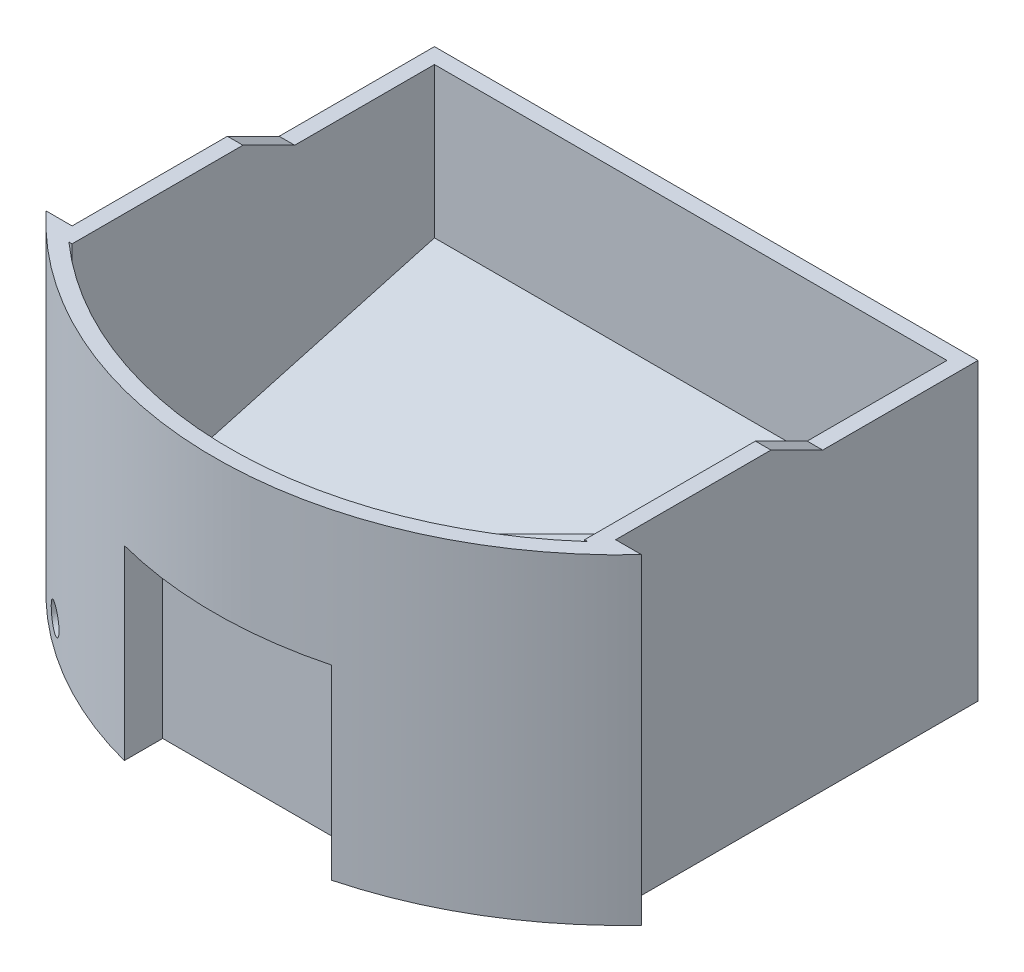
SolidWorks part; units mm, degrees
ref_plane "Front Plane" through (0, 0, 0) normal (0, 0, 1) x (1, 0, 0)
ref_plane "Top Plane" through (0, 0, 0) normal (0, 1, 0) x (1, 0, 0)
ref_plane "Right Plane" through (0, 0, 0) normal (1, 0, 0) x (0, 0, -1)
sketch "Sketch4" plane through (0, 0, 0) normal (0, 1, 0) x (1, 0, 0)
  line L0 (-6.35, 0) -> (139.7, 0)
  line L1 (0, 0) -> (133.35, 0)
  line L2 (0, 0) -> (0, 88.9)
  line L3 (0, 88.9) -> (133.35, 88.9)
  line L4 (133.35, 0) -> (133.35, 88.9)
  arc A1 (-6.35, 0) -> (139.7, 0) centre (66.675, 68.1037) ccw
  point P6 (66.675, -31.75)
  point P9 (66.675, 0)
  dimension "D1" = 133.35
  dimension "D2" = 88.9
  dimension "D3" = 146.05
  dimension "D4" = 6.35
  dimension "D5" = 31.75
extrude "Boss-Extrude2" add sketch "Sketch4" along normal blind 78.74 contours L0 A1 | L0 L4 L3 L2 region at (66.675, 0, 12.8907) region at (66.675, 0, -44.45)
sketch "Sketch5" plane through (0, 0, 0) normal (1, 0, 0) x (0, 0, -1)
  line L0 (0, 78.74) -> (88.9, 78.74) construction
  line L1 (0, 78.74) -> (88.9, 78.74)
  line L2 (88.9, 78.74) -> (88.9, 72.39)
  line L3 (88.9, 78.74) -> (88.9, 0) construction
  line L4 (88.9, 72.39) -> (50.8, 72.39)
  line L5 (50.8, 72.39) -> (38.1, 78.74)
  line L6 (38.1, 78.74) -> (88.9, 78.74)
  dimension "D1" = 12.7
  dimension "D2" = 38.1
  dimension "D3" = 6.35
extrude "Cut-Extrude4" cut sketch "Sketch5" along normal through all contours L2 L4 L5 L6
ref_plane "Plane1" through (3.81, 0, 0) normal (1, 0, 0) x (0, 0, -1)
ref_plane "Plane2" through (129.54, 0, 0) normal (1, 0, 0) x (0, 0, -1)
ref_plane "Plane3" through (0, 0, -85.09) normal (0, 0, -1) x (-1, 0, 0)
ref_plane "Plane4" through (0, 15.24, 0) normal (0, 1, 0) x (1, 0, 0)
ref_plane "Plane5" through (0, 0, 28.448) normal (0, 0, 1) x (1, 0, 0)
ref_plane "Plane6" through (15.24, 0, 0) normal (1, 0, 0) x (0, 0, -1)
ref_plane "Plane7" through (0, 0, -11.43) normal (0, 0, 1) x (1, 0, 0)
shell "Shell1" thickness 3.81 removed face at (66.675, 78.74, -7.4083) removed face at (66.675, 75.565, -44.45) removed face at (66.675, 72.39, -69.85)
sketch "Sketch8" plane through (0, 15.24, 0) normal (0, 1, 0) x (1, 0, 0)
  line L0 (0, 88.9) -> (133.35, 88.9) construction
  line L1 (133.35, 0) -> (133.35, 88.9) construction
  line L2 (-6.35, 0) -> (139.7, 0) construction
  line L3 (0, 0) -> (0, 88.9) construction
  line L4 (0, 88.9) -> (133.35, 88.9)
  line L5 (133.35, 0) -> (133.35, 88.9)
  line L6 (-6.35, 0) -> (139.7, 0)
  line L7 (0, 0) -> (0, 88.9)
  arc A0 (-6.35, 0) -> (139.7, 0) centre (66.675, 68.1037) ccw construction
  arc A1 (-6.35, 0) -> (139.7, 0) centre (66.675, 68.1037) ccw
extrude "fill in tube area" add sketch "Sketch8" against normal up to surface (15.24 mm away) contours L7 L6 L5 L4 | A1 L6 region at (66.675, 15.24, -44.45) up to plane "Top Plane"
sketch "Sketch7" plane through (3.81, 0, 0) normal (1, 0, 0) x (0, 0, -1)
  line L0 (-28.448, 78.74) -> (0, 15.24)
  line L1 (-28.448, 43.307) -> (-28.448, -43.307) construction
  line L2 (66.3575, 15.24) -> (-66.3575, 15.24) construction
  line L3 (0, 80.3275) -> (0, -80.3275) construction
  line L4 (0, 15.24) -> (-28.448, 15.24)
  line L5 (-28.448, 15.24) -> (-28.448, 78.74)
  line L6 (0, 78.74) -> (-31.75, 78.74) construction
extrude "Front inner slope" add sketch "Sketch7" along normal up to surface (125.73 mm away) up to plane "Plane2"
sketch "Sketch11" plane through (0, 15.24, 0) normal (0, 1, 0) x (1, 0, 0)
  line L0 (3.81, -43.307) -> (3.81, 43.307) construction
  line L1 (-6.35, 0) -> (139.7, 0) construction
  circle A0 centre (9.525, 5.715) radius 3.175
  dimension "D1" = 6.35
  dimension "D2" = 5.715
  dimension "D3" = 5.715
extrude "Cut-Extrude6" cut sketch "Sketch11" against normal blind 10.16
sketch "Sketch12" plane through (0, 0, -85.09) normal (0, 0, -1) x (-1, 0, 0)
  line L0 (-129.54, 35.56) -> (-15.24, 15.24)
  line L1 (-129.54, 43.307) -> (-129.54, -43.307) construction
  line L2 (-15.24, 43.307) -> (-15.24, -43.307) construction
  line L3 (66.3575, 15.24) -> (-66.3575, 15.24) construction
  line L4 (-15.24, 15.24) -> (-129.54, 15.24)
  line L5 (-129.54, 15.24) -> (-129.54, 35.56)
  dimension "D1" = 20.32
extrude "Inner Slope 1" add sketch "Sketch12" against normal up to surface (113.538 mm away) up to plane "Plane5"
sketch "Sketch9" plane through (0, 15.24, 0) normal (0, 1, 0) x (1, 0, 0)
  line L2 (-6.35, 0) -> (-6.35, -28.448)
  line L3 (-43.307, -28.448) -> (43.307, -28.448) construction
  line L4 (-6.35, -28.448) -> (41.2087, -28.448)
  line L5 (139.7, -28.448) -> (139.7, 0)
  line L6 (92.1413, -28.448) -> (139.7, -28.448)
  arc A0 (-6.35, 0) -> (139.7, 0) centre (66.675, 68.1037) ccw construction
  arc A1 (-6.35, 0) -> (41.2087, -28.448) centre (66.675, 68.1037) ccw
  arc A2 (92.1413, -28.448) -> (139.7, 0) centre (66.675, 68.1037) ccw
extrude "Remove extra inner slope material" cut sketch "Sketch9" along normal through all
sketch "Sketch13" plane through (3.81, 0, 0) normal (1, 0, 0) x (0, 0, -1)
  line L0 (85.09, 35.56) -> (11.43, 15.24)
  line L1 (85.09, -39.8145) -> (85.09, 39.8145) construction
  line L2 (11.43, 43.307) -> (11.43, -43.307) construction
  line L3 (66.3575, 15.24) -> (-66.3575, 15.24) construction
  line L4 (11.43, 15.24) -> (85.09, 15.24)
  line L5 (85.09, 15.24) -> (85.09, 35.56)
  dimension "D1" = 20.32
extrude "Inner Slope 2" add sketch "Sketch13" along normal up to surface (125.73 mm away) up to plane "Plane2"
sketch "Sketch14" plane through (0, 0, 0) normal (0, 0, 1) x (1, 0, 0)
  line L0 (0, -43.307) -> (0, 43.307) construction
  line L1 (66.3575, 15.24) -> (-66.3575, 15.24) construction
  circle A0 centre (9.525, 6.985) radius 3.175
  dimension "D3" = 6.35
  dimension "D1" = 9.525
  dimension "D2" = 8.255
extrude "Cut-Extrude7" cut sketch "Sketch14" against normal blind 8.89 and the other way through all
sketch "Sketch15" plane through (0, 0, 0) normal (0, 1, 0) x (1, 0, 0)
  line L0 (0, 88.9) -> (133.35, 88.9) construction
  line L1 (19.05, 88.9) -> (23.368, 88.9)
  line L2 (19.05, 88.9) -> (19.05, -6.35)
  line L3 (19.05, -6.35) -> (23.368, -6.35)
  line L4 (23.368, 88.9) -> (23.368, -6.35)
  line L5 (133.35, 0) -> (133.35, 88.9) construction
  line L6 (114.3, 88.9) -> (109.982, 88.9)
  line L7 (114.3, 88.9) -> (114.3, -6.35)
  line L8 (114.3, -6.35) -> (109.982, -6.35)
  line L9 (109.982, 88.9) -> (109.982, -6.35)
  line L10 (0, 0) -> (0, 88.9) construction
  line L12 (-6.35, 0) -> (139.7, 0) construction
  dimension "D1" = 4.318
  dimension "D2" = 4.318
  dimension "D3" = 19.05
  dimension "D4" = 19.05
  dimension "D5" = 6.35
extrude "rails" cut sketch "Sketch15" along normal blind 3.556
ref_plane "Plane8" through (0, 0, 19.05) normal (0, 0, 1) x (1, 0, 0)
sketch "Sketch16" plane through (0, 0, 0) normal (0, 1, 0) x (1, 0, 0)
  line L0 (-43.307, -19.05) -> (43.307, -19.05) construction
  line L2 (41.275, -24.5204) -> (41.275, -19.05)
  line L3 (41.275, -19.05) -> (92.075, -19.05)
  line L4 (92.075, -24.5204) -> (92.075, -19.05)
  arc A0 (3.81, -4.5075) -> (124.3556, -8.6905) centre (66.675, 68.1037) ccw construction
  arc A1 (41.275, -24.5204) -> (92.075, -24.5204) centre (66.675, 68.1037) ccw
  arc A2 (-6.35, 0) -> (139.7, 0) centre (66.675, 68.1037) ccw construction
  point P10 (66.675, -19.05)
  point P14 (66.675, -31.75)
  dimension "D1" = 50.8
extrude "Inner hand grip" cut sketch "Sketch16" along normal blind 57.15
sketch "Sketch17" plane through (0, 0, 0) normal (0, 1, 0) x (1, 0, 0)
  line L0 (41.275, -24.5204) -> (41.275, -28.4655)
  line L1 (92.075, -24.5204) -> (92.075, -28.4655)
  arc A0 (41.275, -24.5204) -> (92.075, -24.5204) centre (66.675, 68.1037) ccw
  arc A1 (3.81, -4.5075) -> (124.3556, -8.6905) centre (66.675, 68.1037) ccw construction
  arc A2 (41.275, -28.4655) -> (92.075, -28.4655) centre (66.675, 68.1037) ccw
  arc A3 (-6.35, 0) -> (139.7, 0) centre (66.675, 68.1037) ccw construction
  point P9 (66.675, -31.75)
  point P13 (66.675, -27.94)
  dimension "D1" = 50.8
extrude "Outer hand grip" cut sketch "Sketch17" along normal blind 45.72
